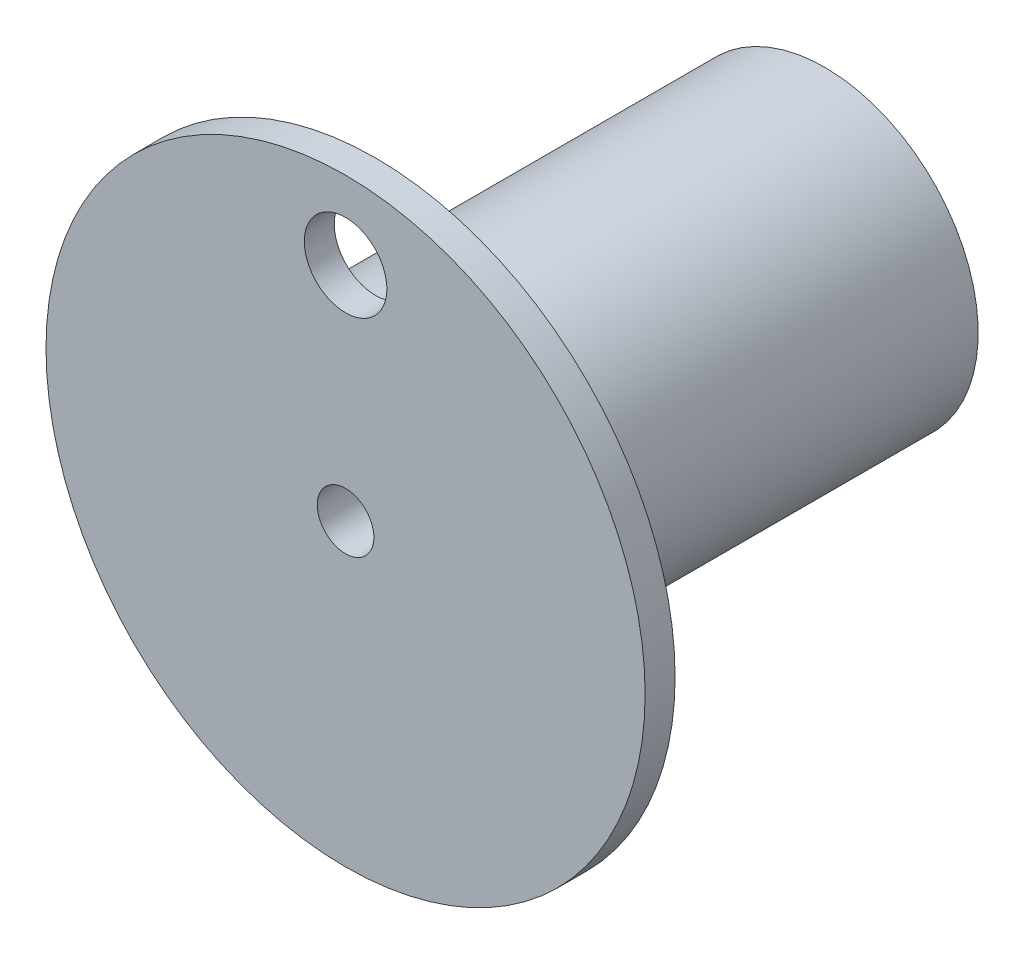
SolidWorks part; units mm, degrees
ref_plane "Front Plane" through (0, 0, 0) normal (0, 0, 1) x (1, 0, 0)
ref_plane "Top Plane" through (0, 0, 0) normal (0, 1, 0) x (1, 0, 0)
ref_plane "Right Plane" through (0, 0, 0) normal (1, 0, 0) x (0, 0, -1)
sketch "Sketch1" plane through (0, 0, 0) normal (0, 0, 1) x (1, 0, 0)
  circle A0 centre (0, 0) radius 6.5
  dimension "D1" = 13
extrude "Boss-Extrude1" add sketch "Sketch1" along normal blind 19.05
sketch "Sketch2" plane through (0, 0, 19.05) normal (0, 0, 1) x (1, 0, 0)
  circle A0 centre (0, 0) radius 12.7
  dimension "D1" = 25.4
extrude "Boss-Extrude2" add sketch "Sketch2" along normal blind 1.27
sketch "Sketch3" plane through (0, 0, 0) normal (0, 0, -1) x (-1, 0, 0)
  circle A0 centre (0, 0) radius 1.2
  dimension "D1" = 2.4
extrude "Cut-Extrude1" cut sketch "Sketch3" against normal through all
sketch "Sketch4" plane through (0, 0, 19.05) normal (0, 0, -1) x (-1, 0, 0)
  circle A0 centre (0, 9.398) radius 1.75
  circle A1 centre (0, 0) radius 12.7 construction
  dimension "D1" = 3.5
  dimension "D2" = 9.398
extrude "Cut-Extrude2" cut sketch "Sketch4" against normal blind 7.62
